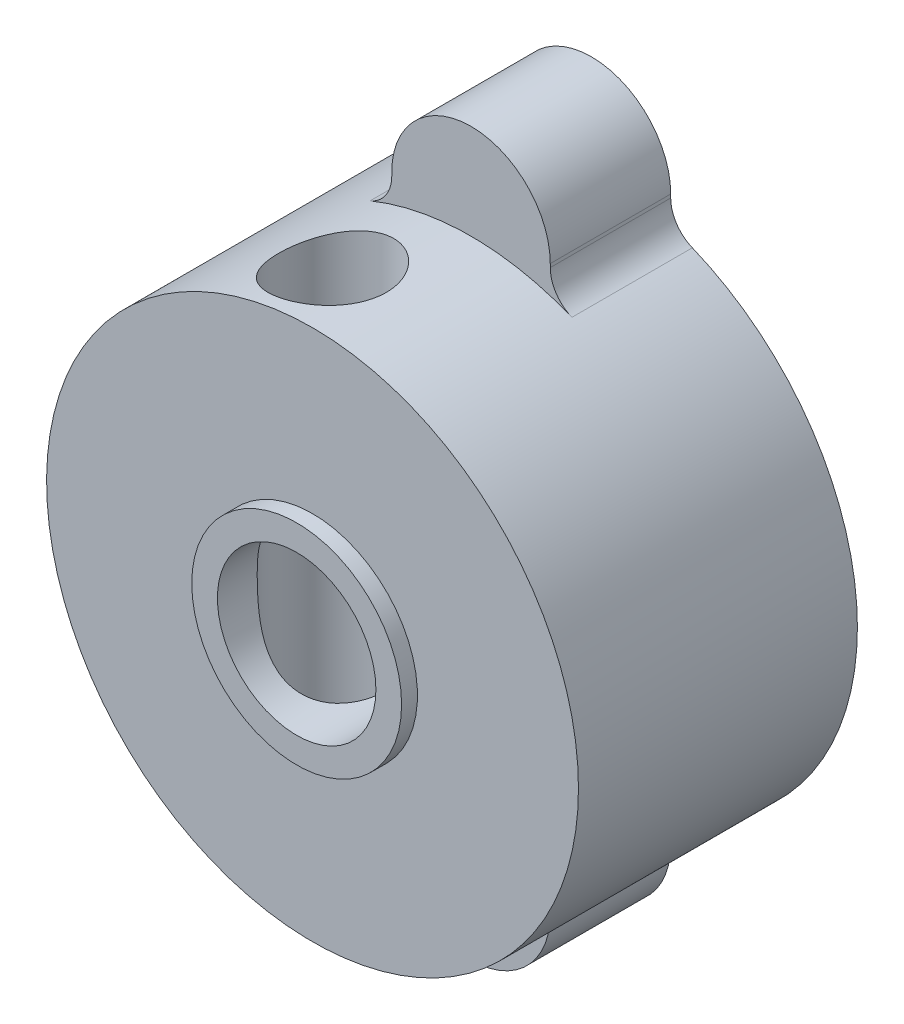
SolidWorks part; units mm, degrees
ref_plane "Front Plane" through (0, 0, 0) normal (0, 0, 1) x (1, 0, 0)
ref_plane "Top Plane" through (0, 0, 0) normal (0, 1, 0) x (1, 0, 0)
ref_plane "Right Plane" through (0, 0, 0) normal (1, 0, 0) x (0, 0, -1)
sketch "Sketch1" plane through (0, 0, 0) normal (0, 0, 1) x (1, 0, 0)
  line L7 (2.5, 8.89) -> (2.5, 8.7807)
  line L8 (-2.5, 8.89) -> (-2.5, 8.7807)
  line L10 (-2.5, -8.89) -> (-2.5, -8.7807)
  line L11 (2.5, -8.89) -> (2.5, -8.7807)
  arc A10 (-3.1827, 7.7629) -> (-3.1827, -7.7629) centre (0, 0) ccw
  arc A13 (2.5, 8.7807) -> (3.1827, 7.7629) centre (3.6, 8.7807) ccw
  arc A14 (-3.1827, 7.7629) -> (-2.5, 8.7807) centre (-3.6, 8.7807) ccw
  arc A15 (-3.1827, -7.7629) -> (-2.5, -8.7807) centre (-3.6, -8.7807) cw
  arc A16 (2.5, -8.7807) -> (3.1827, -7.7629) centre (3.6, -8.7807) cw
  arc A19 (3.1827, -7.7629) -> (3.1827, 7.7629) centre (0, 0) ccw
  arc A28 (2.5, 8.89) -> (-2.5, 8.89) centre (0, 8.89) ccw
  arc A29 (-2.5, -8.89) -> (2.5, -8.89) centre (0, -8.89) ccw
extrude "Boss-Extrude1" add sketch "Sketch1" along normal blind 8.8
sketch "Sketch2" plane through (0, 0, 8.8) normal (0, 0, 1) x (1, 0, 0)
  circle A0 centre (0, 0) radius 8.39
  circle A1 centre (0, 0) radius 2.5
extrude "Cut-Extrude1" cut sketch "Sketch2" against normal offset from surface (5 mm away) 3.8 flip side to cut up to face at (0, 0, 0)
sketch "Sketch3" plane through (0, 0, 0) normal (0, 1, 0) x (1, 0, 0)
  circle A0 centre (-1.5, -6.67) radius 1.7
extrude "Cut-Extrude2" cut sketch "Sketch3" against normal through all both and the other way through all
sketch "Sketch4" plane through (0, 0, 8.8) normal (0, 0, 1) x (1, 0, 0)
  circle A0 centre (0, 0) radius 2.5
  circle A1 centre (0, 0) radius 3.31
extrude "Boss-Extrude2" add sketch "Sketch4" along normal blind 0.5
